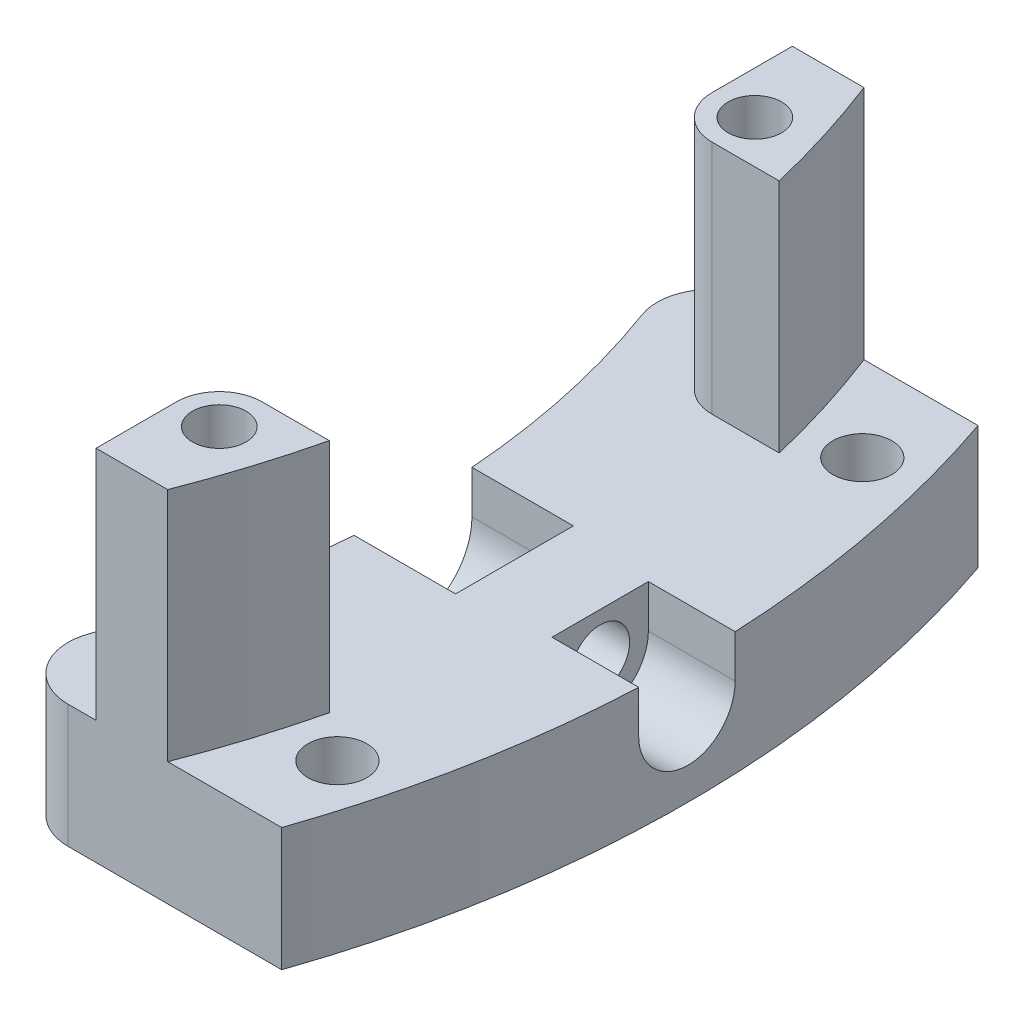
SolidWorks part; units mm, degrees
ref_plane "Front Plane" through (0, 0, 0) normal (0, 0, 1) x (1, 0, 0)
ref_plane "Top Plane" through (0, 0, 0) normal (0, 1, 0) x (1, 0, 0)
ref_plane "Right Plane" through (0, 0, 0) normal (1, 0, 0) x (0, 0, -1)
sketch "Sketch1" plane through (0, 0, 0) normal (0, 1, 0) x (1, 0, 0)
  line L0 (67.0714, -32.5) -> (94.5714, -32.5)
  line L1 (67.0714, 32.5) -> (94.5714, 32.5)
  line L2 (0, -32.5) -> (67.0714, -32.5) construction
  line L3 (-6.4979, 32.5) -> (67.0714, 32.5) construction
  line L6 (0, 32.5) -> (94.5714, 32.5) construction
  arc A0 (94.5714, 32.5) -> (94.5714, -32.5) centre (0, 0) cw
  arc A1 (67.0714, 32.5) -> (67.0714, -32.5) centre (0, 0) cw
  circle A2 centre (0, 0) radius 32.5 construction
  dimension "D1" = 100
  dimension "D3" = 27.5
  dimension "D4" = 65
extrude "Boss-Extrude1" add sketch "Sketch1" along normal blind 11.5
sketch "Sketch2" plane through (0, 11.5, 0) normal (0, -1, 0) x (1, 0, 0)
  line L0 (67.0714, 32.5) -> (94.5714, 32.5) construction
  line L1 (94.5714, -32.5) -> (67.0714, -32.5) construction
  line L2 (94.5714, -32.5) -> (67.0714, -32.5) construction
  line L3 (81.2404, 21) -> (87.5157, 21)
  line L4 (77.2404, 25) -> (77.2404, 32.5)
  line L5 (67.0714, 32.5) -> (94.5714, 32.5) construction
  line L6 (77.2404, 32.5) -> (83.9271, 32.5)
  line L7 (77.2404, -25) -> (77.2404, -32.5)
  line L8 (81.2404, -21) -> (87.5157, -21)
  line L9 (83.9271, -32.5) -> (77.2404, -32.5)
  arc A0 (83.9271, 32.5) -> (83.9271, -32.5) centre (0, 0) cw construction
  arc A1 (94.5714, -32.5) -> (94.5714, 32.5) centre (0, 0) ccw construction
  arc A2 (77.2404, 25) -> (81.2404, 21) centre (81.2404, 25) ccw
  circle A3 centre (81.2404, 25) radius 5 construction
  arc A4 (81.2404, -21) -> (77.2404, -25) centre (81.2404, -25) ccw
  circle A5 centre (81.2404, -25) radius 5 construction
  arc A6 (83.9271, 32.5) -> (87.5157, 21) centre (0, 0) cw
  arc A7 (83.9271, -32.5) -> (87.5157, -21) centre (0, 0) ccw
  dimension "D1" = 10
  dimension "D2" = 10
  dimension "D4" = 8
  dimension "D5" = 7.5
  dimension "D3" = 7.5
extrude "Boss-Extrude2" add sketch "Sketch2" against normal offset from surface (22 mm away) 22
sketch "Sketch3" plane through (0, 33.5, 0) normal (0, 1, 0) x (1, 0, 0)
  circle A0 centre (81.2404, 25) radius 2.5
  circle A1 centre (81.2404, -25) radius 2.5
  dimension "D1" = 5
extrude "Cut-Extrude1" cut sketch "Sketch3" against normal blind 4
sketch "Sketch4" plane through (0, 0, 0) normal (0, -1, 0) x (1, 0, 0)
  circle A0 centre (91.7683, 24.5) radius 4.5
  circle A1 centre (91.7683, -24.5) radius 4.5
  dimension "D1" = 9
extrude "Cut-Extrude2" cut sketch "Sketch4" against normal blind 5
sketch "Sketch5" plane through (0, 5, 0) normal (0, -1, 0) x (1, 0, 0)
  circle A0 centre (91.7683, 24.5) radius 2.75
  circle A1 centre (91.7683, -24.5) radius 2.75
  dimension "D1" = 5.5
extrude "Cut-Extrude3" cut sketch "Sketch5" against normal through all
ref_plane "Plane1" through (67.0714, 0, 0) normal (-1, 0, 0) x (0, 0, 1)
sketch "Sketch6" plane through (67.0714, 0, 0) normal (-1, 0, 0) x (0, 0, 1)
  line L1 (32.5, 11.5) -> (-32.5, 11.5) construction
  circle A0 centre (0, 7.5) radius 5 construction
  circle A1 centre (0, 7.5) radius 2.75
  circle A2 centre (0, 7.5) radius 4.5 construction
  dimension "D1" = 10
  dimension "D2" = 4
  dimension "D3" = 5.5
  dimension "D4" = 9
extrude "Cut-Extrude4" cut sketch "Sketch6" against normal through all
ref_plane "Plane2" through (100, 0, 0) normal (1, 0, 0) x (0, 0, -1)
ref_plane "Plane3" through (83.5357, 0, 0) normal (1, 0, 0) x (0, 0, -1)
sketch "Sketch8" plane through (100, 0, 0) normal (1, 0, 0) x (0, 0, -1)
  line L0 (-4.5, 7.5) -> (-4.5, 11.5)
  line L1 (32.5, 11.5) -> (-32.5, 11.5) construction
  line L2 (4.5, 7.5) -> (4.5, 11.5)
  line L3 (4.5, 11.5) -> (-4.5, 11.5)
  arc A1 (-4.5, 7.5) -> (4.5, 7.5) centre (0, 7.5) ccw
  dimension "D1" = 9
extrude "Cut-Extrude5" cut sketch "Sketch8" against normal blind 8.2
sketch "Sketch7" plane through (0, 11.5, 0) normal (0, 1, 0) x (1, 0, 0)
  line L1 (71.8, 5.5) -> (71.8, -5.5) construction
  line L2 (0, 0) -> (71.8, 0) construction
  line L3 (71.8, 5.5) -> (96.8, 5.5) construction
  line L4 (96.8, 5.5) -> (96.8, -5.5) construction
  line L5 (96.8, -5.5) -> (71.8, -5.5) construction
  line L7 (91.8, 4.5) -> (91.8, -4.5) construction
  line L10 (71.8, 5.5) -> (71.8, -5.5)
  line L11 (71.8, -5.5) -> (83.8, -5.5)
  line L12 (83.8, -5.5) -> (83.8, 5.5)
  line L13 (83.8, 5.5) -> (71.8, 5.5)
  line L14 (91.8, 5.5) -> (91.8, -5.5) construction
  line L15 (91.8, 4.5) -> (91.8, -4.5) construction
  line L16 (67.0714, -32.5) -> (77.2404, -32.5) construction
  line L17 (77.2404, 32.5) -> (67.0714, 32.5) construction
  arc A1 (73.101, 32.5) -> (73.101, -32.5) centre (0, 0) cw construction
  point P15 (91.8, 0)
  dimension "D3" = 12
  dimension "D5" = 80
  dimension "D1" = 11
  dimension "D2" = 25
  dimension "D4" = 5
extrude "Cut-Extrude6" cut sketch "Sketch7" against normal blind 9.5
fillet "Fillet1" radius 5.5 2 edges at (79.0637, 2, 5.5) (79.0637, 2, -5.5)
fillet "Fillet2" radius 5 2 edges at (67.0714, 5.75, 32.5) (67.0714, 5.75, -32.5)
